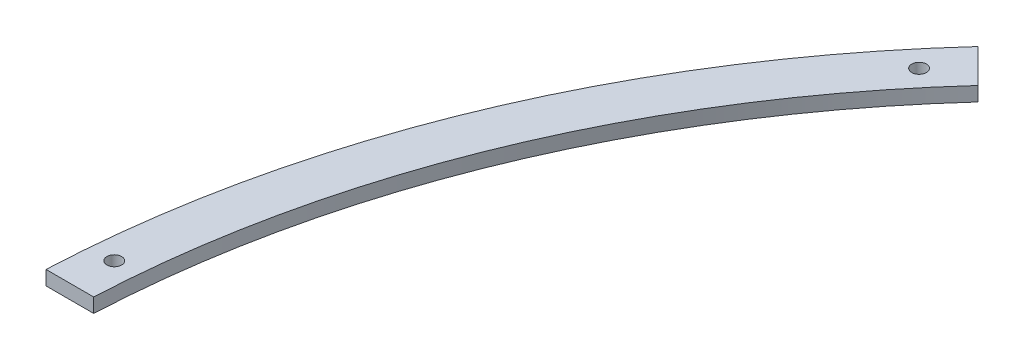
SolidWorks part; units mm, degrees
ref_plane "Front Plane" through (0, 0, 0) normal (0, 0, 1) x (1, 0, 0)
ref_plane "Top Plane" through (0, 0, 0) normal (0, 1, 0) x (1, 0, 0)
ref_plane "Right Plane" through (0, 0, 0) normal (1, 0, 0) x (0, 0, -1)
sketch "Sketch1" plane through (0, 0, 0) normal (0, 1, 0) x (1, 0, 0)
  line L1 (0, 220) -> (0, -220) construction
  line L6 (-220, 0) -> (220, 0) construction
  line L7 (-10, 219.7726) -> (-10, -219.7726) construction
  line L12 (-10, 219.7726) -> (-10, 209.7618)
  line L13 (-219.7726, 10) -> (219.7726, 10) construction
  line L14 (-219.7726, 10) -> (-209.7618, 10)
  line L15 (-155.5635, 155.5635) -> (155.5635, -155.5635) construction
  line L16 (-162.4738, 148.3316) -> (148.3316, -162.4738)
  arc A3 (-10, 219.7726) -> (-219.7726, 10) centre (0, 0) ccw
  arc A4 (-10, 209.7618) -> (-209.7618, 10) centre (0, 0) ccw
  arc A5 (-210, 0) -> (-209.7618, 10) centre (0, 0) ccw construction
  arc A6 (-220, 0) -> (-219.7726, 10) centre (0, 0) ccw construction
  circle A7 centre (0, 0) radius 215 construction
  dimension "D1" = 210
  dimension "D2" = 220
  dimension "D4" = 10
  dimension "D5" = 5
  dimension "D3" = 10
  dimension "D6" = 20
sketch "Sketch14" [suppressed] plane through (0, 0, 0) normal (0, 1, 0) x (1, 0, 0)
  line L0 (-200, 10) -> (200, 10) construction
  line L1 (-10, 200) -> (-10, -200) construction
  line L2 (-200, 10) -> (-189.7367, 10)
  line L3 (-10, 200) -> (-10, 189.7367)
  circle A0 centre (0, 0) radius 200 construction
  circle A1 centre (0, 0) radius 190 construction
  arc A2 (-10, 199.7498) -> (-199.7498, 10) centre (0, 0) ccw
  arc A3 (-10, 189.7367) -> (-189.7367, 10) centre (0, 0) ccw
sketch "roll" plane through (0, 0, 0) normal (0, 1, 0) x (1, 0, 0)
  line L0 (0, -195) -> (0, 195) construction
  dimension "D1" = 390
ref_axis "Axis1" through (0, -148.0362, 0) along (0, 1, 0)
extrude "base" add sketch "Sketch1" along normal mid plane 3 contours A4 L15 A3 L14 region at (-194.7302, 0, -80.6599)
sketch "Sketch25" plane through (0, 1.5, 0) normal (0, 1, 0) x (1, 0, 0)
  line L0 (-220, 0) -> (220, 0) construction
  line L1 (0, 220) -> (0, -220) construction
  line L2 (-220, 0) -> (220, 0)
  line L3 (0, 220) -> (0, -220)
  line L4 (0, 0) -> (-214.1819, 18.7385) construction
  line L6 (-155.5635, 155.5635) -> (155.5635, -155.5635) construction
  line L7 (-155.5635, 155.5635) -> (155.5635, -155.5635)
  line L8 (0, 0) -> (-164.6996, 138.1993) construction
  circle A0 centre (0, 0) radius 215 construction
  circle A1 centre (0, 0) radius 215 construction
  dimension "D1" = 5
  dimension "D3" = 5
ref_plane "Plane1" through (0, 0, 0) normal (0.7071, 0, -0.7071) x (0.7071, 0, 0.7071)
hole_wizard "Ø3.1 (3.1) Diameter Hole1" positions "Sketch28" profile "Sketch29" hole size "Ø3.1" standard "ISO" end condition through all
sketch "Sketch28" plane through (0, 1.5, 0) normal (0, 1, 0) x (1, 0, 0)
  point P0 (-214.1819, 18.7385)
  point P3 (-164.6996, 138.1993)
sketch "Sketch29" plane through (-214.1819, 1.5, -18.7385) normal (1, 0, 0) x (0, 0, 1)
  line L0 (0, 0) -> (0, 3)
  line L1 (0, 3) -> (1.55, 3)
  line L2 (1.55, 3) -> (1.55, 0)
  line L5 (1.55, 0) -> (0, 0)
  line L11 (0, -6.35) -> (0, 107.95) construction
  dimension "Thru Hole Dia." = 3.1
  dimension "Thru Hole Depth" = 3
